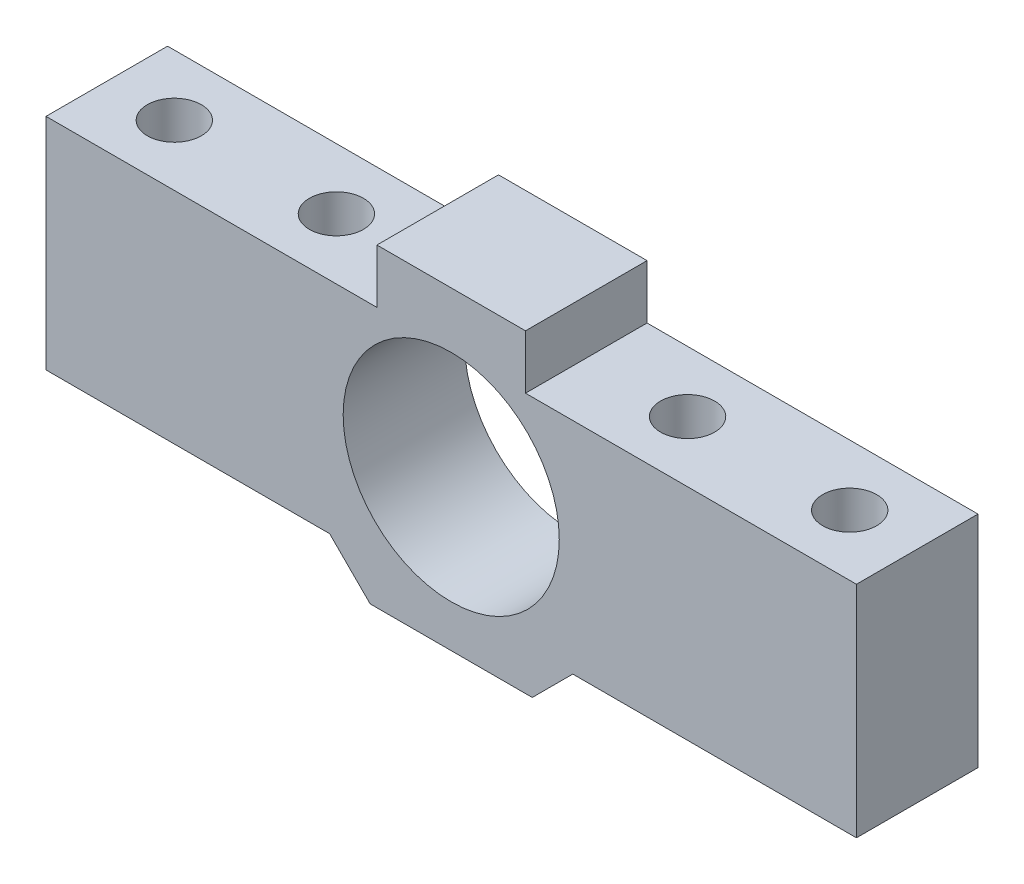
SolidWorks part; units mm, degrees
ref_plane "Front" through (0, 0, 0) normal (0, 0, 1) x (1, 0, 0)
ref_plane "Top" through (0, 0, 0) normal (0, 1, 0) x (1, 0, 0)
ref_plane "Right" through (0, 0, 0) normal (1, 0, 0) x (0, 0, -1)
sketch "Esquisse1" plane through (0, 0, 0) normal (0, 0, 1) x (1, 0, 0)
  line L0 (0, 8.13) -> (60, 8.13) construction
  line L1 (0, 0) -> (60, 0)
  line L2 (0, 0) -> (0, 16.26)
  line L3 (0, 16.26) -> (60, 16.26)
  line L4 (60, 0) -> (60, 16.26)
  circle A0 centre (30, 8.13) radius 8
  dimension "D3" = 16
  dimension "D1" = 16.26
  dimension "D2" = 60
extrude "Boss.-Extru.1" add sketch "Esquisse1" along normal blind 9
sketch "Esquisse2" plane through (0, 0, 9) normal (0, 0, 1) x (1, 0, 0)
  line L0 (60, 16.26) -> (0, 16.26) construction
  line L1 (24.5, 16.26) -> (35.5, 16.26)
  line L2 (24.5, 16.26) -> (24.5, 20.26)
  line L3 (24.5, 20.26) -> (35.5, 20.26)
  line L4 (35.5, 16.26) -> (35.5, 20.26)
  line L5 (30, 20.26) -> (30, 0) construction
  line L6 (0, 0) -> (60, 0) construction
  dimension "D1" = 11
  dimension "D2" = 4
extrude "Boss.-Extru.2" add sketch "Esquisse2" against normal up to vertex (9 mm away) up to point (60, 16.26, 0)
sketch "Esquisse3" plane through (0, 0, 9) normal (0, 0, 1) x (1, 0, 0)
  line L0 (0, 0) -> (60, 0) construction
  line L1 (24, 0) -> (36, 0)
  line L2 (24, 0) -> (24, -3)
  line L3 (24, -3) -> (36, -3)
  line L4 (36, 0) -> (36, -3)
  line L5 (30, -3) -> (30, 8.13) construction
  dimension "D1" = 3
  dimension "D2" = 12
extrude "Boss.-Extru.3" add sketch "Esquisse3" against normal up to vertex (9 mm away) up to point (0, 0, 0)
chamfer "Chanfrein2" distance 3 angle 45 2 edges at (36, 0, 4.5) (24, 0, 4.5)
sketch "Esquisse4" plane through (0, 0, 0) normal (0, -1, 0) x (1, 0, 0)
  line L0 (0, 4.5) -> (17, 4.5) construction
  line L1 (0, 9) -> (0, 0) construction
  line L2 (30, 0) -> (30, 9) construction
  line L3 (24, 0) -> (36, 0) construction
  line L4 (24, 9) -> (36, 9) construction
  line L5 (60, 4.5) -> (43, 4.5) construction
  circle A0 centre (17, 4.5) radius 2
  circle A1 centre (5, 4.5) radius 2
  circle A2 centre (55, 4.5) radius 2
  circle A3 centre (43, 4.5) radius 2
  dimension "D1" = 4
  dimension "D2" = 12
  dimension "D3" = 26
extrude "Enlèv. mat.-Extru.1" cut sketch "Esquisse4" against normal through all
